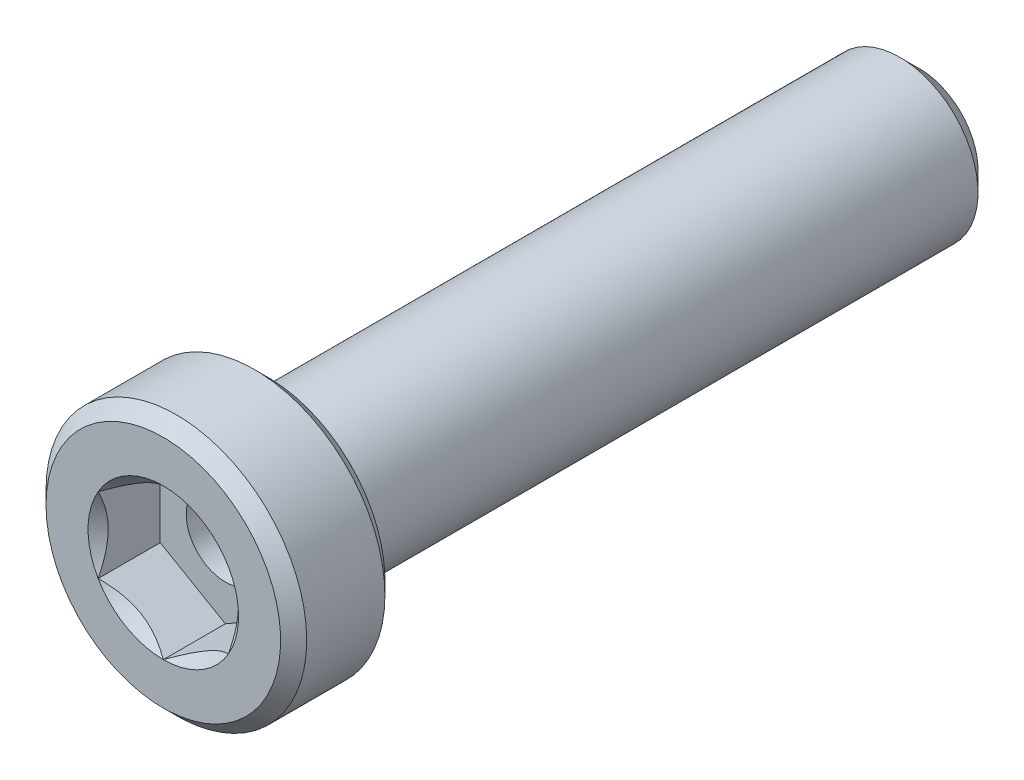
SolidWorks part; units mm, degrees
ref_plane "Front Plane" through (0, 0, 0) normal (0, 0, 1) x (1, 0, 0)
ref_plane "Top Plane" through (0, 0, 0) normal (0, 1, 0) x (1, 0, 0)
ref_plane "Right Plane" through (0, 0, 0) normal (1, 0, 0) x (0, 0, -1)
sketch "Sketch1" plane through (0, 0, 0) normal (-1, 0, 0) x (0, 0, 1)
  line L0 (0, -3) -> (25, -3) construction
  line L1 (0, 0) -> (25, 0)
  line L2 (0, 0) -> (0, 3)
  line L3 (0, 3) -> (25, 3)
  line L4 (25, 0) -> (25, 3)
  line L5 (25, 0) -> (29, 0)
  line L6 (25, 0) -> (25, 5)
  line L7 (25, 5) -> (29, 5)
  line L8 (29, 0) -> (29, 5)
  line L9 (25, -5) -> (29, -5) construction
  dimension "Head Diameter" = 10
  dimension "OD" = 6
  dimension "Length" = 25
  dimension "Head Height" = 4
revolve "Revolve1" add sketch "Sketch1" angle 360 about L5 region at (0, 1.5, 12.5) region at (0, 2.5, 27)
chamfer "Chamfer1" distance 0.5 angle 45 2 edges at (-5, 0, 25) (-5, 0, 29)
sketch "Sketch2" plane through (0, 0, 29) normal (0, 0, 1) x (1, 0, 0)
  line L1 (0, 2.8868) -> (-2.5, 1.4434)
  line L2 (-2.5, 1.4434) -> (-2.5, -1.4434)
  line L3 (-2.5, -1.4434) -> (0, -2.8868)
  line L4 (0, -2.8868) -> (2.5, -1.4434)
  line L5 (2.5, -1.4434) -> (2.5, 1.4434)
  line L6 (2.5, 1.4434) -> (0, 2.8868)
  circle A0 centre (0, 0) radius 2.5 construction
  dimension "Hex Size" = 5
extrude "Cut-Extrude1" cut sketch "Sketch2" against normal blind 2.38
sketch "Sketch3" plane through (0, 0, 11.32) normal (-1, 0, 0) x (0, 0, 1)
  line L0 (15.3, 1.4434) -> (15.3, -1.4434) construction
  line L1 (15.3, 1.4434) -> (15.3, -1.4434) construction
  line L2 (13.6195, 1.5) -> (12.92, 0)
  line L3 (15.3, 0) -> (12.92, 0)
  line L6 (13.6195, 1.5) -> (15.3, 1.5)
  line L7 (15.3, 1.5) -> (15.3, 0)
  line L8 (13.6195, -1.5) -> (15.3, -1.5) construction
  dimension "D1" = 65
  dimension "Pilot Recess Diameter" = 3
  dimension "D2" = 2.38
revolve "Cut-Revolve1" cut sketch "Sketch3" angle 360 about L3
sketch "Sketch4" plane through (0, 0, 29) normal (0, 0, 1) x (1, 0, 0)
  circle A0 centre (0, 0) radius 2.8868
extrude "Cut-Extrude2" cut sketch "Sketch4" against normal through all draft 45
sketch "Sketch5" plane through (0, 0, 0) normal (1, 0, 0) x (0, 0, -1)
  line L0 (-19.5, 3) -> (-19.5, -3)
  line L1 (0, 3) -> (-25, 3) construction
  line L2 (-25, -3) -> (0, -3) construction
  line L3 (0, -3) -> (0, 3) construction
  dimension "Min Thread Length" = 19.5
split "Split1" trim tools "Sketch5" bodies to split 106 resulting bodies 107 108
sketch "Sketch6" plane through (0, 0, 0) normal (0, 0, 1) x (1, 0, 0)
  circle A1 centre (0, 0) radius 3
  circle A2 centre (0, 0) radius 3
  dimension "D1" = 0
curve "Helix/Spiral1" pitch 1 height 20.5 turns 20.5 parameters "Pitch"=1
chamfer "Chamfer2" distance 0.75 angle 45 1 edges at (-3, 0, 0)
sketch "Sketch9" plane through (0, 0, 0) normal (1, 0, 0) x (0, 0, -1)
  line L1 (0, 3) -> (0, -3)
  line L2 (0, 3) -> (0, -3)
  spline S1 degree 3 poles (0, 3) (-0.0207, 3) (-0.0626, 2.8438) (-0.125, 2.1765) (-0.1875, 1.1779) (-0.25, 0) (-0.3125, -1.1779) (-0.375, -2.1765) (-0.4375, -2.8438) (-0.5, -3.0781) (-0.5625, -2.8438) (-0.625, -2.1765) (-0.6875, -1.1779) (-0.75, 0) (-0.8125, 1.1779) (-0.875, 2.1765) (-0.9375, 2.8438) (-1, 3.0781) (-1.0625, 2.8438) (-1.125, 2.1765) (-1.1875, 1.1779) (-1.25, 0) (-1.3125, -1.1779) (-1.375, -2.1765) (-1.4375, -2.8438) (-1.5, -3.0781) (-1.5625, -2.8438) (-1.625, -2.1765) (-1.6875, -1.1779) (-1.75, 0) (-1.8125, 1.1779) (-1.875, 2.1765) (-1.9375, 2.8438) (-2, 3.0781) (-2.0625, 2.8438) (-2.125, 2.1765) (-2.1875, 1.1779) (-2.25, 0) (-2.3125, -1.1779) (-2.375, -2.1765) (-2.4375, -2.8438) (-2.5, -3.0781) (-2.5625, -2.8438) (-2.625, -2.1765) (-2.6875, -1.1779) (-2.75, 0) (-2.8125, 1.1779) (-2.875, 2.1765) (-2.9375, 2.8438) (-3, 3.0781) (-3.0625, 2.8438) (-3.125, 2.1765) (-3.1875, 1.1779) (-3.25, 0) (-3.3125, -1.1779) (-3.375, -2.1765) (-3.4375, -2.8438) (-3.5, -3.0781) (-3.5625, -2.8438) (-3.625, -2.1765) (-3.6875, -1.1779) (-3.75, 0) (-3.8125, 1.1779) (-3.875, 2.1765) (-3.9375, 2.8438) (-4, 3.0781) (-4.0625, 2.8438) (-4.125, 2.1765) (-4.1875, 1.1779) (-4.25, 0) (-4.3125, -1.1779) (-4.375, -2.1765) (-4.4375, -2.8438) (-4.5, -3.0781) (-4.5625, -2.8438) (-4.625, -2.1765) (-4.6875, -1.1779) (-4.75, 0) (-4.8125, 1.1779) (-4.875, 2.1765) (-4.9375, 2.8438) (-5, 3.0781) (-5.0625, 2.8438) (-5.125, 2.1765) (-5.1875, 1.1779) (-5.25, 0) (-5.3125, -1.1779) (-5.375, -2.1765) (-5.4375, -2.8438) (-5.5, -3.0781) (-5.5625, -2.8438) (-5.625, -2.1765) (-5.6875, -1.1779) (-5.75, 0) (-5.8125, 1.1779) (-5.875, 2.1765) (-5.9375, 2.8438) (-6, 3.0781) (-6.0625, 2.8438) (-6.125, 2.1765) (-6.1875, 1.1779) (-6.25, 0) (-6.3125, -1.1779) (-6.375, -2.1765) (-6.4375, -2.8438) (-6.5, -3.0781) (-6.5625, -2.8438) (-6.625, -2.1765) (-6.6875, -1.1779) (-6.75, 0) (-6.8125, 1.1779) (-6.875, 2.1765) (-6.9375, 2.8438) (-7, 3.0781) (-7.0625, 2.8438) (-7.125, 2.1765) (-7.1875, 1.1779) (-7.25, 0) (-7.3125, -1.1779) (-7.375, -2.1765) (-7.4375, -2.8438) (-7.5, -3.0781) (-7.5625, -2.8438) (-7.625, -2.1765) (-7.6875, -1.1779) (-7.75, 0) (-7.8125, 1.1779) (-7.875, 2.1765) (-7.9375, 2.8438) (-8, 3.0781) (-8.0625, 2.8438) (-8.125, 2.1765) (-8.1875, 1.1779) (-8.25, 0) (-8.3125, -1.1779) (-8.375, -2.1765) (-8.4375, -2.8438) (-8.5, -3.0781) (-8.5625, -2.8438) (-8.625, -2.1765) (-8.6875, -1.1779) (-8.75, 0) (-8.8125, 1.1779) (-8.875, 2.1765) (-8.9375, 2.8438) (-9, 3.0781) (-9.0625, 2.8438) (-9.125, 2.1765) (-9.1875, 1.1779) (-9.25, 0) (-9.3125, -1.1779) (-9.375, -2.1765) (-9.4375, -2.8438) (-9.5, -3.0781) (-9.5625, -2.8438) (-9.625, -2.1765) (-9.6875, -1.1779) (-9.75, 0) (-9.8125, 1.1779) (-9.875, 2.1765) (-9.9375, 2.8438) (-10, 3.0781) (-10.0625, 2.8438) (-10.125, 2.1765) (-10.1875, 1.1779) (-10.25, 0) (-10.3125, -1.1779) (-10.375, -2.1765) (-10.4375, -2.8438) (-10.5, -3.0781) (-10.5625, -2.8438) (-10.625, -2.1765) (-10.6875, -1.1779) (-10.75, 0) (-10.8125, 1.1779) (-10.875, 2.1765) (-10.9375, 2.8438) (-11, 3.0781) (-11.0625, 2.8438) (-11.125, 2.1765) (-11.1875, 1.1779) (-11.25, 0) (-11.3125, -1.1779) (-11.375, -2.1765) (-11.4375, -2.8438) (-11.5, -3.0781) (-11.5625, -2.8438) (-11.625, -2.1765) (-11.6875, -1.1779) (-11.75, 0) (-11.8125, 1.1779) (-11.875, 2.1765) (-11.9375, 2.8438) (-12, 3.0781) (-12.0625, 2.8438) (-12.125, 2.1765) (-12.1875, 1.1779) (-12.25, 0) (-12.3125, -1.1779) (-12.375, -2.1765) (-12.4375, -2.8438) (-12.5, -3.0781) (-12.5625, -2.8438) (-12.625, -2.1765) (-12.6875, -1.1779) (-12.75, 0) (-12.8125, 1.1779) (-12.875, 2.1765) (-12.9375, 2.8438) (-13, 3.0781) (-13.0625, 2.8438) (-13.125, 2.1765) (-13.1875, 1.1779) (-13.25, 0) (-13.3125, -1.1779) (-13.375, -2.1765) (-13.4375, -2.8438) (-13.5, -3.0781) (-13.5625, -2.8438) (-13.625, -2.1765) (-13.6875, -1.1779) (-13.75, 0) (-13.8125, 1.1779) (-13.875, 2.1765) (-13.9375, 2.8438) (-14, 3.0781) (-14.0625, 2.8438) (-14.125, 2.1765) (-14.1875, 1.1779) (-14.25, 0) (-14.3125, -1.1779) (-14.375, -2.1765) (-14.4375, -2.8438) (-14.5, -3.0781) (-14.5625, -2.8438) (-14.625, -2.1765) (-14.6875, -1.1779) (-14.75, 0) (-14.8125, 1.1779) (-14.875, 2.1765) (-14.9375, 2.8438) (-15, 3.0781) (-15.0625, 2.8438) (-15.125, 2.1765) (-15.1875, 1.1779) (-15.25, 0) (-15.3125, -1.1779) (-15.375, -2.1765) (-15.4375, -2.8438) (-15.5, -3.0781) (-15.5625, -2.8438) (-15.625, -2.1765) (-15.6875, -1.1779) (-15.75, 0) (-15.8125, 1.1779) (-15.875, 2.1765) (-15.9375, 2.8438) (-16, 3.0781) (-16.0625, 2.8438) (-16.125, 2.1765) (-16.1875, 1.1779) (-16.25, 0) (-16.3125, -1.1779) (-16.375, -2.1765) (-16.4375, -2.8438) (-16.5, -3.0781) (-16.5625, -2.8438) (-16.625, -2.1765) (-16.6875, -1.1779) (-16.75, 0) (-16.8125, 1.1779) (-16.875, 2.1765) (-16.9375, 2.8438) (-17, 3.0781) (-17.0625, 2.8438) (-17.125, 2.1765) (-17.1875, 1.1779) (-17.25, 0) (-17.3125, -1.1779) (-17.375, -2.1765) (-17.4375, -2.8438) (-17.5, -3.0781) (-17.5625, -2.8438) (-17.625, -2.1765) (-17.6875, -1.1779) (-17.75, 0) (-17.8125, 1.1779) (-17.875, 2.1765) (-17.9375, 2.8438) (-18, 3.0781) (-18.0625, 2.8438) (-18.125, 2.1765) (-18.1875, 1.1779) (-18.25, 0) (-18.3125, -1.1779) (-18.375, -2.1765) (-18.4375, -2.8438) (-18.5, -3.0781) (-18.5625, -2.8438) (-18.625, -2.1765) (-18.6875, -1.1779) (-18.75, 0) (-18.8125, 1.1779) (-18.875, 2.1765) (-18.9375, 2.8438) (-19, 3.0781) (-19.0625, 2.8438) (-19.125, 2.1765) (-19.1875, 1.1779) (-19.25, 0) (-19.3125, -1.1779) (-19.375, -2.1765) (-19.4375, -2.8438) (-19.5, -3.0781) (-19.5625, -2.8438) (-19.625, -2.1765) (-19.6875, -1.1779) (-19.75, 0) (-19.8125, 1.1779) (-19.875, 2.1765) (-19.9375, 2.8438) (-20, 3.0781) (-20.0625, 2.8438) (-20.125, 2.1765) (-20.1875, 1.1779) (-20.25, 0) (-20.3125, -1.1779) (-20.375, -2.1765) (-20.4374, -2.8438) (-20.4793, -3) (-20.5, -3) knots 0 0 0 0 0.003049 0.006098 0.009146 0.012195 0.015244 0.018293 0.021341 0.02439 0.027439 0.030488 0.033537 0.036585 0.039634 0.042683 0.045732 0.04878 0.051829 0.054878 0.057927 0.060976 0.064024 0.067073 0.070122 0.073171 0.07622 0.079268 0.082317 0.085366 0.088415 0.091463 0.094512 0.097561 0.10061 0.103659 0.106707 0.109756 0.112805 0.115854 0.118902 0.121951 0.125 0.128049 0.131098 0.134146 0.137195 0.140244 0.143293 0.146341 0.14939 0.152439 0.155488 0.158537 0.161585 0.164634 0.167683 0.170732 0.17378 0.176829 0.179878 0.182927 0.185976 0.189024 0.192073 0.195122 0.198171 0.20122 0.204268 0.207317 0.210366 0.213415 0.216463 0.219512 0.222561 0.22561 0.228659 0.231707 0.234756 0.237805 0.240854 0.243902 0.246951 0.25 0.253049 0.256098 0.259146 0.262195 0.265244 0.268293 0.271341 0.27439 0.277439 0.280488 0.283537 0.286585 0.289634 0.292683 0.295732 0.29878 0.301829 0.304878 0.307927 0.310976 0.314024 0.317073 0.320122 0.323171 0.32622 0.329268 0.332317 0.335366 0.338415 0.341463 0.344512 0.347561 0.35061 0.353659 0.356707 0.359756 0.362805 0.365854 0.368902 0.371951 0.375 0.378049 0.381098 0.384146 0.387195 0.390244 0.393293 0.396341 0.39939 0.402439 0.405488 0.408537 0.411585 0.414634 0.417683 0.420732 0.42378 0.426829 0.429878 0.432927 0.435976 0.439024 0.442073 0.445122 0.448171 0.45122 0.454268 0.457317 0.460366 0.463415 0.466463 0.469512 0.472561 0.47561 0.478659 0.481707 0.484756 0.487805 0.490854 0.493902 0.496951 0.5 0.503049 0.506098 0.509146 0.512195 0.515244 0.518293 0.521341 0.52439 0.527439 0.530488 0.533537 0.536585 0.539634 0.542683 0.545732 0.54878 0.551829 0.554878 0.557927 0.560976 0.564024 0.567073 0.570122 0.573171 0.57622 0.579268 0.582317 0.585366 0.588415 0.591463 0.594512 0.597561 0.60061 0.603659 0.606707 0.609756 0.612805 0.615854 0.618902 0.621951 0.625 0.628049 0.631098 0.634146 0.637195 0.640244 0.643293 0.646341 0.64939 0.652439 0.655488 0.658537 0.661585 0.664634 0.667683 0.670732 0.67378 0.676829 0.679878 0.682927 0.685976 0.689024 0.692073 0.695122 0.698171 0.70122 0.704268 0.707317 0.710366 0.713415 0.716463 0.719512 0.722561 0.72561 0.728659 0.731707 0.734756 0.737805 0.740854 0.743902 0.746951 0.75 0.753049 0.756098 0.759146 0.762195 0.765244 0.768293 0.771341 0.77439 0.777439 0.780488 0.783537 0.786585 0.789634 0.792683 0.795732 0.79878 0.801829 0.804878 0.807927 0.810976 0.814024 0.817073 0.820122 0.823171 0.82622 0.829268 0.832317 0.835366 0.838415 0.841463 0.844512 0.847561 0.85061 0.853659 0.856707 0.859756 0.862805 0.865854 0.868902 0.871951 0.875 0.878049 0.881098 0.884146 0.887195 0.890244 0.893293 0.896341 0.89939 0.902439 0.905488 0.908537 0.911585 0.914634 0.917683 0.920732 0.92378 0.926829 0.929878 0.932927 0.935976 0.939024 0.942073 0.945122 0.948171 0.95122 0.954268 0.957317 0.960366 0.963415 0.966463 0.969512 0.972561 0.97561 0.978659 0.981707 0.984756 0.987805 0.990854 0.993902 0.996951 1 1 1 1 construction
  point P2 (-3.5, -3)
  dimension "D2" = 3.5
sketch "Sketch7" [suppressed] plane through (0, 0, 0) normal (1, 0, 0) x (0, 0, -1)
  line L0 (-0.0577, 3.1) -> (0, 3)
  line L1 (0, 3) -> (0.375, 2.3505)
  line L2 (0.375, 2.3505) -> (0.5, 2.3505)
  line L3 (0.5, 2.3505) -> (0.875, 3)
  line L4 (0.875, 3) -> (0.9327, 3.1)
  line L5 (0.9327, 3.1) -> (-0.0577, 3.1)
  line L6 (0, 3) -> (0.875, 3) construction
  line L7 (0.6875, 2.6752) -> (0.1875, 2.6752) construction
  line L8 (0.4375, 2.3505) -> (0.4375, 3.1) construction
  dimension "D1" = 0.1
  dimension "D2" = 0.125
  dimension "D3" = 0.5
  dimension "D4" = 60
sweep "Cut-Sweep1" [suppressed] cut profiles "Sketch7" path "Helix/Spiral1"
sketch "Sketch8" [suppressed] plane through (0, 0, 19.5) normal (0, 0, -1) x (-1, 0, 0)
  circle A1 centre (0, 0) radius 3
  circle A2 centre (0, 0) radius 3
  dimension "D1" = 0
extrude "Boss-Extrude1" [suppressed] add sketch "Sketch8" along normal through all draft 45
combine bodies "Combine1" operation type add bodies to combine 107 108
ref_axis "Center Axis 1" through (0, 0, 29.3405) along (0, 0, -1)
ref_plane "Contact Plane 1" through (0, 0, 0) normal (0, 0, -1) x (-1, 0, 0)
ref_plane "Contact Plane 2" through (0, 0, 25) normal (0, 0, -1) x (-1, 0, 0)
ref_plane "Contact Plane 3" through (0, 0, 26.62) normal (0, 0, 1) x (1, 0, 0)
ref_plane "Contact Plane 4" through (0, 0, 29) normal (0, 0, 1) x (1, 0, 0)
ref_plane "Thread Engagement Plane" through (0, 0, 19.5) normal (0, 0, 1) x (1, 0, 0)
equation "\"D1@Chamfer1\"=\"Head Diameter@Sketch1\"*.05"
equation "\"D3@Helix/Spiral1\" = \"Pitch@Helix/Spiral1\" + \"Min Thread Length@Sketch5\""
equation "\"D1@Chamfer2\"=\"Pitch@Helix/Spiral1\"*.75"
equation "\"D2@Sketch7\"=\"Pitch@Helix/Spiral1\"/8"
equation "\"D3@Sketch7\"=\"Pitch@Helix/Spiral1\"/2"
equation "\"D2@Sketch3\"=\"Hex Depth@Cut-Extrude1\""
equation "\"D2@Sketch9\"=\"Pitch@Helix/Spiral1\"*3.5"
